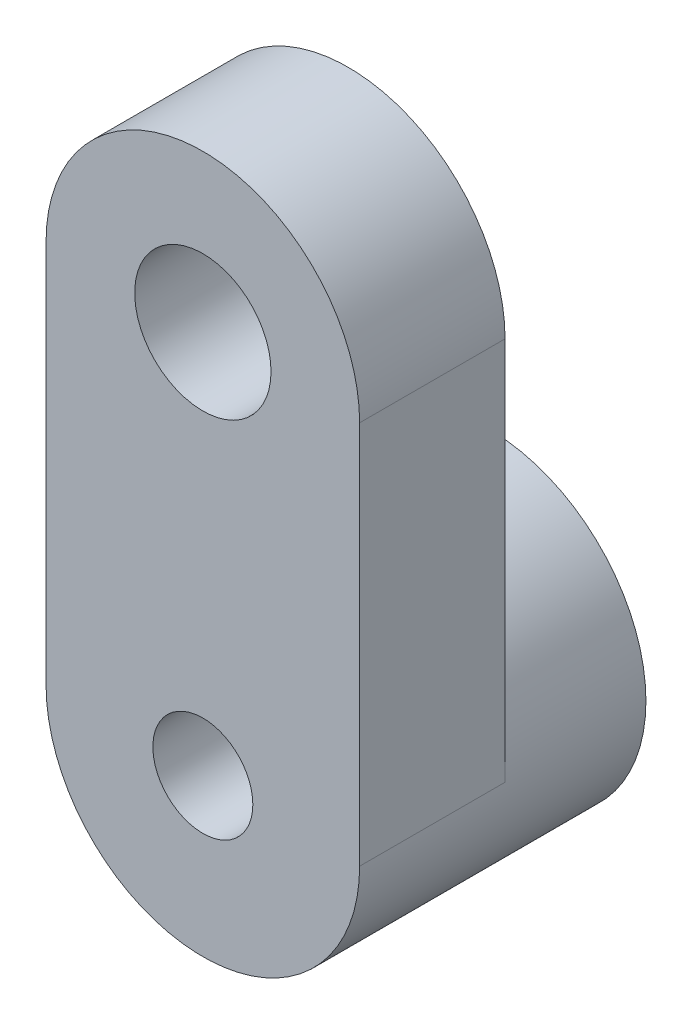
SolidWorks part; units mm, degrees
ref_plane "Front Plane" through (0, 0, 0) normal (0, 0, 1) x (1, 0, 0)
ref_plane "Top Plane" through (0, 0, 0) normal (0, 1, 0) x (1, 0, 0)
ref_plane "Right Plane" through (0, 0, 0) normal (1, 0, 0) x (0, 0, -1)
sketch "Sketch1" plane through (0, 0, 0) normal (0, 0, 1) x (1, 0, 0)
  circle A0 centre (0, 0) radius 2.525
  circle A1 centre (0, 0) radius 3.45
  dimension "D1" = 5.05
  dimension "D2" = 6.9
extrude "Boss-Extrude1" add sketch "Sketch1" along normal blind 6.3
sketch "Sketch2" plane through (0, 0, 6.3) normal (0, 0, 1) x (1, 0, 0)
  circle A1 centre (0, 0) radius 1.1
  circle A2 centre (0, 0) radius 2.525 construction
  circle A3 centre (0, 0) radius 2.525
  dimension "D1" = 2.2
extrude "Boss-Extrude2" add sketch "Sketch2" against normal blind 3.2
ref_axis "Axis1" through (0, 0, 3.1) along (0, 0, 1)
sketch "Sketch3" plane through (0, 0, 0) normal (0, 0, -1) x (-1, 0, 0)
  line L3 (0, 0.2085) -> (0, 4.7758) construction
  line L4 (-0.1, 2.525) -> (0.1, 2.525)
  line L5 (0.1, 2.525) -> (0, 2.425)
  line L6 (0, 2.425) -> (-0.1, 2.525)
  circle A3 centre (0, 0) radius 2.525 construction
  circle A4 centre (0, 0) radius 2.525
  point P5 (0, 2.525)
  circle M5 centre (0, 0) radius 2.525
  dimension "D1" = 0.1
extrude "Boss-Extrude4" add sketch "Sketch3" against normal up to surface (3.1 mm away) contours L6 L3 M5 | L3 L5 M5 region at (0.0328, 2.4912, 0) region at (-0.0328, 2.4912, 0) up to face at (1.1, 0, 3.1)
pattern_circular "CirPattern3" count 60 over 360 about axis through (0, 0, 3.1) along (0, 0, 1) of "Boss-Extrude4"
sketch "Sketch4" plane through (0, 0, 6.3) normal (0, 0, 1) x (1, 0, 0)
  line L0 (-3.45, 0) -> (-3.45, 8.45)
  line L1 (3.45, 8.45) -> (3.45, 0)
  circle A0 centre (0, 0) radius 3.45 construction
  arc A1 (-3.45, 8.45) -> (3.45, 8.45) centre (0, 8.45) cw
  circle A2 centre (0, 0) radius 3.45
  circle M1 centre (0, 0) radius 3.45
  dimension "D1" = 8.45
extrude "Boss-Extrude5" add sketch "Sketch4" against normal blind 3.2 contours A1 L0 L1 M1 region at (0, 6.9346, 6.3)
sketch "Sketch5" plane through (0, 0, 6.3) normal (0, 0, 1) x (1, 0, 0)
  circle A0 centre (0, 8.45) radius 1.5
  arc A1 (3.45, 8.45) -> (-3.45, 8.45) centre (0, 8.45) ccw construction
  arc A2 (3.45, 8.45) -> (-3.45, 8.45) centre (0, 8.45) ccw
  dimension "D1" = 3
extrude "Cut-Extrude1" cut sketch "Sketch5" against normal blind 10 contours A0 region at (0, 8.45, 6.3)
